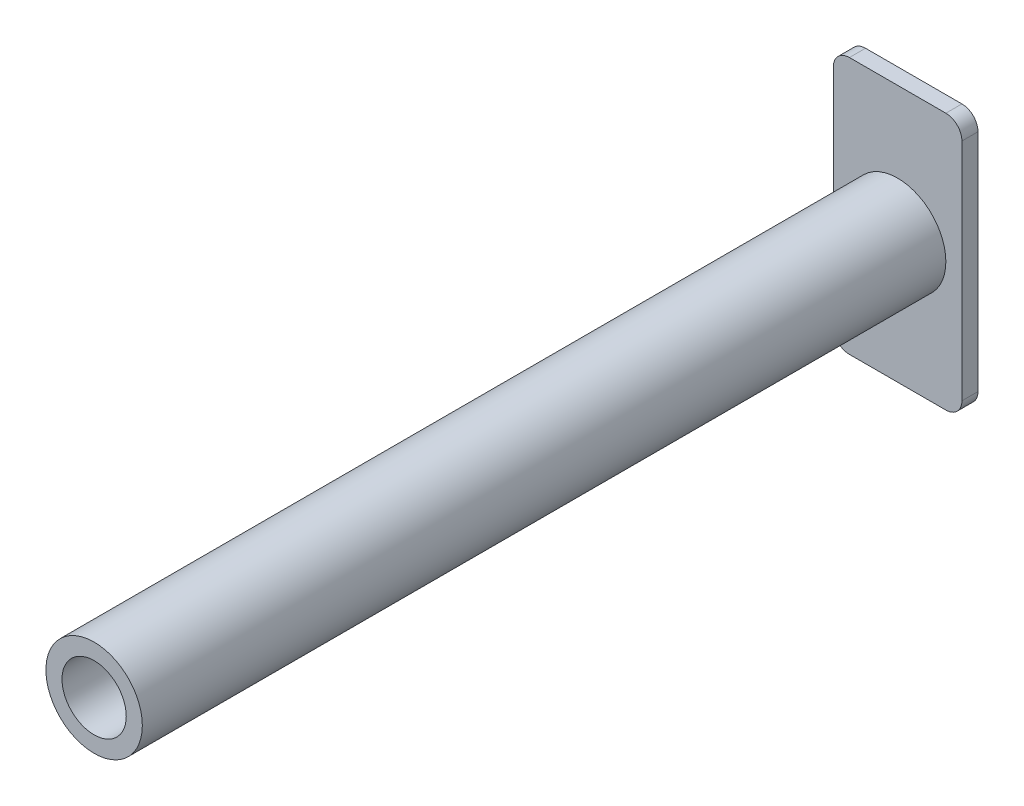
SolidWorks part; units mm, degrees
ref_plane "Front Plane" through (0, 0, 0) normal (0, 0, 1) x (1, 0, 0)
ref_plane "Top Plane" through (0, 0, 0) normal (0, 1, 0) x (1, 0, 0)
ref_plane "Right Plane" through (0, 0, 0) normal (1, 0, 0) x (0, 0, -1)
sketch "Plate Sketch" plane through (0, 0, 0) normal (0, 0, 1) x (1, 0, 0)
  line L0 (0, 101) -> (0, -101) construction
  line L1 (-40, 80) -> (40, 80)
  line L2 (-40, 80) -> (-40, -80)
  line L3 (-40, -80) -> (40, -80)
  line L4 (40, 80) -> (40, -80)
  line L5 (-40, 80) -> (40, -80) construction
  line L6 (-40, -80) -> (40, 80) construction
  point P0 (0, 0)
  point P9 (0, 0)
  dimension "D1" = 80
  dimension "D2" = 160
  dimension "D3" = 202
extrude "Plate Extrude" add sketch "Plate Sketch" along normal blind 10
fillet "Plate Fillet" radius 10 4 edges at (40, -80, 5) (-40, -80, 5) (-40, 80, 5) (40, 80, 5)
sketch "Pole Sketch" plane through (0, 0, 10) normal (0, 0, 1) x (1, 0, 0)
  circle A0 centre (0, 0) radius 30
  circle A1 centre (0, 0) radius 20
  dimension "D1" = 10
  dimension "D2" = 60
extrude "Pole Extrude" add sketch "Pole Sketch" along normal blind 500
